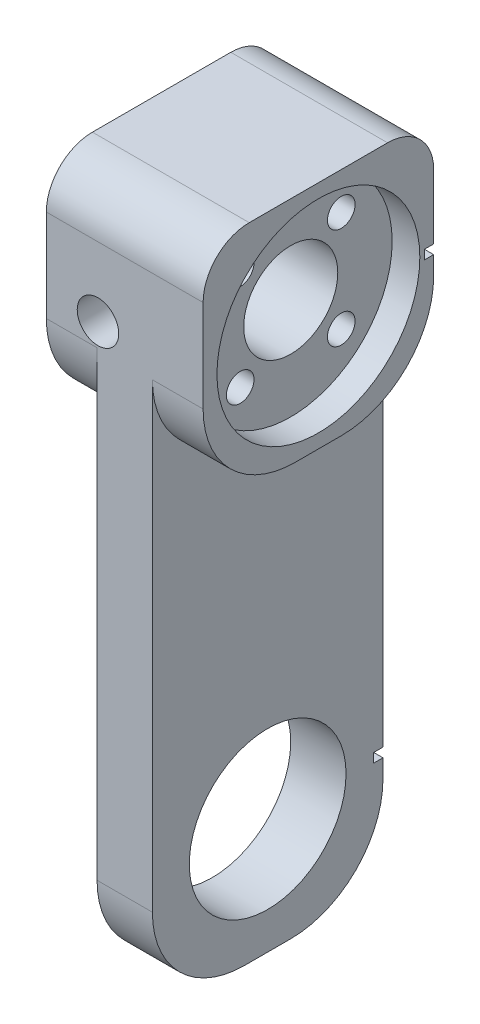
SolidWorks part; units mm, degrees
ref_plane "Alzado" through (0, 0, 0) normal (0, 0, 1) x (1, 0, 0)
ref_plane "Planta" through (0, 0, 0) normal (0, 1, 0) x (1, 0, 0)
ref_plane "Vista lateral" through (0, 0, 0) normal (1, 0, 0) x (0, 0, -1)
sketch "Croquis1" plane through (0, 0, 0) normal (0, 1, 0) x (1, 0, 0)
  line L1 (0, 0) -> (25, 0)
  line L2 (0, 0) -> (0, 25)
  line L3 (0, 25) -> (25, 25)
  line L4 (25, 0) -> (25, 25)
  dimension "D1" = 25
  dimension "D2" = 25
extrude "Saliente-Extruir1" add sketch "Croquis1" along normal blind 200
fillet "Redondeo1" radius 10 1 edges at (12.5, 0, -25) type face fillet first side face at (12.5, 0, -12.5) second side face at (12.5, 100, -25)
fillet "Redondeo2" radius 10 1 edges at (12.5, 0, 0) type face fillet first side face at (12.5, 100, 0) second side face at (12.5, 0, -7.5)
fillet "Redondeo3" radius 5 1 edges at (12.5, 200, 0) type face fillet first side face at (12.5, 105, 0) second side face at (12.5, 200, -12.5)
fillet "Redondeo4" radius 5 1 edges at (12.5, 200, -25) type face fillet first side face at (12.5, 200, -15) second side face at (12.5, 105, -25)
sketch "Croquis2" plane through (25, 0, 0) normal (1, 0, 0) x (0, 0, -1)
  line L0 (5, 200) -> (20, 200) construction
  line L1 (25, 195) -> (25, 10) construction
  circle A0 centre (12.5, 187.5) radius 11
  circle A1 centre (12.5, 137.5) radius 8.5
  dimension "D2" = 22
  dimension "D5" = 17
  dimension "D1" = 12.5
  dimension "D3" = 12.5
  dimension "D4" = 50
  dimension "D6" = 12.5
extrude "Cortar-Extruir1" cut sketch "Croquis2" against normal blind 6
sketch "Croquis3" plane through (0, 0, 0) normal (-1, 0, 0) x (0, 0, 1)
  line L0 (-25, 195) -> (-25, 10) construction
  line L2 (-15, 0) -> (-10, 0) construction
  circle A0 centre (-12.5, 12.5) radius 8.5
  circle A1 centre (-12.5, 187.5) radius 8.5
  dimension "D1" = 17
  dimension "D5" = 17
  dimension "D2" = 12.5
  dimension "D3" = 12.5
  dimension "D4" = 175
  dimension "D6" = 12.5
extrude "Cortar-Extruir2" cut sketch "Croquis3" against normal blind 6
sketch "Croquis9" plane through (19, 0, 0) normal (1, 0, 0) x (0, 0, -1)
  circle A0 centre (12.5, 187.5) radius 5.1
  circle A1 centre (12.5, 137.5) radius 6
  dimension "D1" = 10.2
  dimension "D2" = 12
extrude "Cortar-Extruir6" cut sketch "Croquis9" against normal blind 30
ref_plane "Plano1" through (12.5, 0, 0) normal (1, 0, 0) x (0, 0, -1)
sketch "Croquis13" plane through (0, 0, -25) normal (0, 0, -1) x (-1, 0, 0)
  line L0 (0, 195) -> (-25, 195) construction
  line L1 (-13, 189.5473) -> (-12, 189.5473)
  line L2 (-13, 189.5473) -> (-13, 184.5473)
  line L3 (-13, 184.5473) -> (-12, 184.5473)
  line L4 (-12, 189.5473) -> (-12, 184.5473)
  point P6 (-12.5, 195)
  dimension "D1" = 1
  dimension "D2" = 0.5
  dimension "D3" = 5
extrude "Cortar-Extruir8" cut sketch "Croquis13" against normal blind 1
sketch "Croquis14" plane through (19, 0, 0) normal (1, 0, 0) x (0, 0, -1)
  circle A1 centre (12.5, 187.5) radius 11
  circle A2 centre (12.5, 187.5) radius 11
  circle A3 centre (12.5, 187.5) radius 5.1
  dimension "D2" = 10.2
  dimension "D1" = 0
extrude "Saliente-Extruir3" add sketch "Croquis14" along normal blind 3
sketch "Croquis15" plane through (22, 0, 0) normal (1, 0, 0) x (0, 0, -1)
  line L1 (12.5, 187.5) -> (12.5, 175.887) construction
  line L2 (12.5, 187.5) -> (7.0199, 182.0199) construction
  circle A0 centre (12.5, 187.5) radius 7.75 construction
  circle A1 centre (17.9801, 182.0199) radius 1.5
  circle A2 centre (7.0199, 182.0199) radius 1.5
  circle A3 centre (7.0199, 192.9801) radius 1.5
  circle A4 centre (17.9801, 192.9801) radius 1.5
  point P14 (12.5, 187.5)
  dimension "D2" = 3
  dimension "D3" = 15.5
  dimension "D4" = 45
  dimension "D1" = 4
extrude "Cortar-Extruir9" cut sketch "Croquis15" against normal blind 16
sketch "Croquis16" plane through (0, 0, 0) normal (-1, 0, 0) x (0, 0, 1)
  line L0 (-14.83, 192.2518) -> (-15.7744, 195.344)
  line L1 (-17.2518, 185.17) -> (-20.344, 184.2256)
  line L2 (-20.344, 184.2256) -> (-21.0722, 181.0756)
  line L3 (-21.0722, 181.0756) -> (-18.7083, 178.8698)
  line L4 (-18.7083, 178.8698) -> (-15.6161, 179.8142)
  line L5 (-15.6161, 179.8142) -> (-14.8879, 182.9643)
  line L6 (-14.8879, 182.9643) -> (-17.2518, 185.17)
  line L7 (-17.0357, 189.8879) -> (-14.83, 192.2518)
  line L8 (-20.1858, 190.6161) -> (-17.0357, 189.8879)
  line L9 (-21.1302, 193.7083) -> (-20.1858, 190.6161)
  line L10 (-18.9244, 196.0722) -> (-21.1302, 193.7083)
  line L11 (-15.7744, 195.344) -> (-18.9244, 196.0722)
  line L12 (-7.7482, 189.83) -> (-4.656, 190.7744)
  line L13 (-10.1121, 192.0357) -> (-7.7482, 189.83)
  line L14 (-9.3839, 195.1858) -> (-10.1121, 192.0357)
  line L15 (-6.2917, 196.1302) -> (-9.3839, 195.1858)
  line L16 (-3.9278, 193.9244) -> (-6.2917, 196.1302)
  line L17 (-4.656, 190.7744) -> (-3.9278, 193.9244)
  line L18 (-10.17, 182.7482) -> (-9.2256, 179.656)
  line L19 (-7.9643, 185.1121) -> (-10.17, 182.7482)
  line L20 (-4.8142, 184.3839) -> (-7.9643, 185.1121)
  line L21 (-3.8698, 181.2917) -> (-4.8142, 184.3839)
  line L22 (-6.0756, 178.9278) -> (-3.8698, 181.2917)
  line L23 (-9.2256, 179.656) -> (-6.0756, 178.9278)
  circle A0 centre (-17.9801, 182.0199) radius 2.8 construction
  circle A1 centre (-12.5, 187.5) radius 7.75 construction
  circle A2 centre (-12.5, 187.5) radius 8.5 construction
  point P33 (-12.5, 187.5)
  dimension "D2" = 5.6
  dimension "D1" = 4
extrude "Cortar-Extruir10" cut sketch "Croquis16" against normal blind 11
sketch "Croquis18" plane through (25, 0, 0) normal (1, 0, 0) x (0, 0, -1)
  line L0 (25, 195) -> (25, 10) construction
  line L1 (25, 188) -> (24, 188)
  line L2 (25, 188) -> (25, 187)
  line L3 (25, 187) -> (24, 187)
  line L4 (24, 188) -> (24, 187)
  line L6 (25, 138) -> (24, 138)
  line L7 (25, 138) -> (25, 137)
  line L8 (25, 137) -> (24, 137)
  line L9 (24, 138) -> (24, 137)
  circle A0 centre (12.5, 137.5) radius 8.5 construction
  circle A1 centre (12.5, 187.5) radius 5.3994 construction
  point P10 (24, 137.5)
  point P17 (24, 187.5)
  dimension "D1" = 1
  dimension "D2" = 1
  dimension "D3" = 1
  dimension "D4" = 1
extrude "Cortar-Extruir12" cut sketch "Croquis18" against normal up to surface (25 mm away) up to face at (0, 137.5, -18.5)
sketch "Croquis20" plane through (0, 0, 0) normal (-1, 0, 0) x (0, 0, 1)
  line L0 (-15, 0) -> (-10, 0) construction
  line L1 (-4, 25) -> (-21, 25)
  line L2 (-4, 25) -> (-4, 125)
  line L3 (-4, 125) -> (-21, 125)
  line L4 (-21, 25) -> (-21, 125)
  line L5 (-20, 200) -> (-5, 200) construction
  line L6 (-25, 187) -> (-25, 138) construction
  line L7 (0, 195) -> (0, 10) construction
  point P6 (-12.5, 0)
  dimension "D1" = 25
  dimension "D2" = 75
  dimension "D3" = 4
  dimension "D4" = 4
extrude "Cortar-Extruir14" cut sketch "Croquis20" against normal blind 10
sketch "Croquis12" plane through (0, 0, -25) normal (0, 0, -1) x (-1, 0, 0)
  line L0 (-25, 200) -> (-25, 0) construction
  line L1 (-25, 200) -> (0, 200) construction
  circle A0 centre (-13.6, 187.5) radius 2.25
  dimension "D1" = 4.5
  dimension "D2" = 11.4
  dimension "D3" = 12.5
extrude "Cortar-Extruir7" cut sketch "Croquis12" against normal through all
sketch "Croquis21" plane through (0, 0, 0) normal (0, -1, 0) x (1, 0, 0)
  line L1 (37.9699, -28.4286) -> (-20.9449, -28.4286)
  line L2 (37.9699, -28.4286) -> (37.9699, 7.3318)
  line L3 (37.9699, 7.3318) -> (-20.9449, 7.3318)
  line L4 (-20.9449, -28.4286) -> (-20.9449, 7.3318)
extrude "Cortar-Extruir15" cut sketch "Croquis21" against normal up to surface (125 mm away) up to face at (5, 125, -12.5)
sketch "Croquis22" plane through (0, 0, 0) normal (-1, 0, 0) x (0, 0, 1)
  line L1 (-30.2841, 134.8184) -> (3.0025, 134.8184)
  line L2 (-30.2841, 134.8184) -> (-30.2841, 207.7961)
  line L3 (-30.2841, 207.7961) -> (3.0025, 207.7961)
  line L4 (3.0025, 134.8184) -> (3.0025, 207.7961)
extrude "Cortar-Extruir16" cut sketch "Croquis22" against normal blind 8
fillet "Redondeo5" radius 10 2 edges at (12.5, 125, -25) (12.5, 125, 0)
sketch "Croquis24" plane through (19, 0, 0) normal (1, 0, 0) x (0, 0, -1)
  circle A1 centre (12.5, 137.5) radius 8.5
  circle A2 centre (12.5, 137.5) radius 8.5
  dimension "D1" = 0
extrude "Cortar-Extruir18" cut sketch "Croquis24" against normal blind 27
sketch "Croquis25" plane through (25, 0, 0) normal (1, 0, 0) x (0, 0, -1)
  line L0 (0, 195) -> (0, 135) construction
  line L1 (0, 175) -> (26.132, 175)
  line L2 (0, 175) -> (0, 95)
  line L3 (0, 95) -> (26.132, 95)
  line L4 (26.132, 175) -> (26.132, 95)
  line L5 (5, 200) -> (20, 200) construction
  dimension "D1" = 25
  dimension "D2" = 80
extrude "Cortar-Extruir19" cut sketch "Croquis25" against normal blind 5.5
fillet "Redondeo6" radius 10 1 edges at (22.25, 175, -25) type face fillet first side face at (22.25, 175, -12.5) second side face at (15.2068, 176.1421, -25)
fillet "Redondeo7" radius 10 1 edges at (22.25, 175, 0) type face fillet first side face at (22.25, 175, -7.5) second side face at (11.35, 187.5, 0)
sketch "Croquis27" plane through (0, 0, 0) normal (-1, 0, 0) x (0, 0, 1)
  line L0 (0, 195) -> (0, 135) construction
  line L1 (0, 175) -> (-27.9345, 175)
  line L2 (0, 175) -> (0, 95)
  line L3 (0, 95) -> (-27.9345, 95)
  line L4 (-27.9345, 175) -> (-27.9345, 95)
  line L5 (-20, 200) -> (-5, 200) construction
  dimension "D1" = 25
  dimension "D2" = 80
extrude "Cortar-Extruir21" cut sketch "Croquis27" against normal blind 13.5
fillet "Redondeo8" radius 10 1 edges at (10.75, 175, -25) type face fillet first side face at (10.75, 175, -12.5) second side face at (14.9629, 177.4075, -25)
fillet "Redondeo9" radius 10 1 edges at (10.75, 175, 0) type face fillet first side face at (10.75, 175, -7.5) second side face at (11.35, 187.5, 0)
